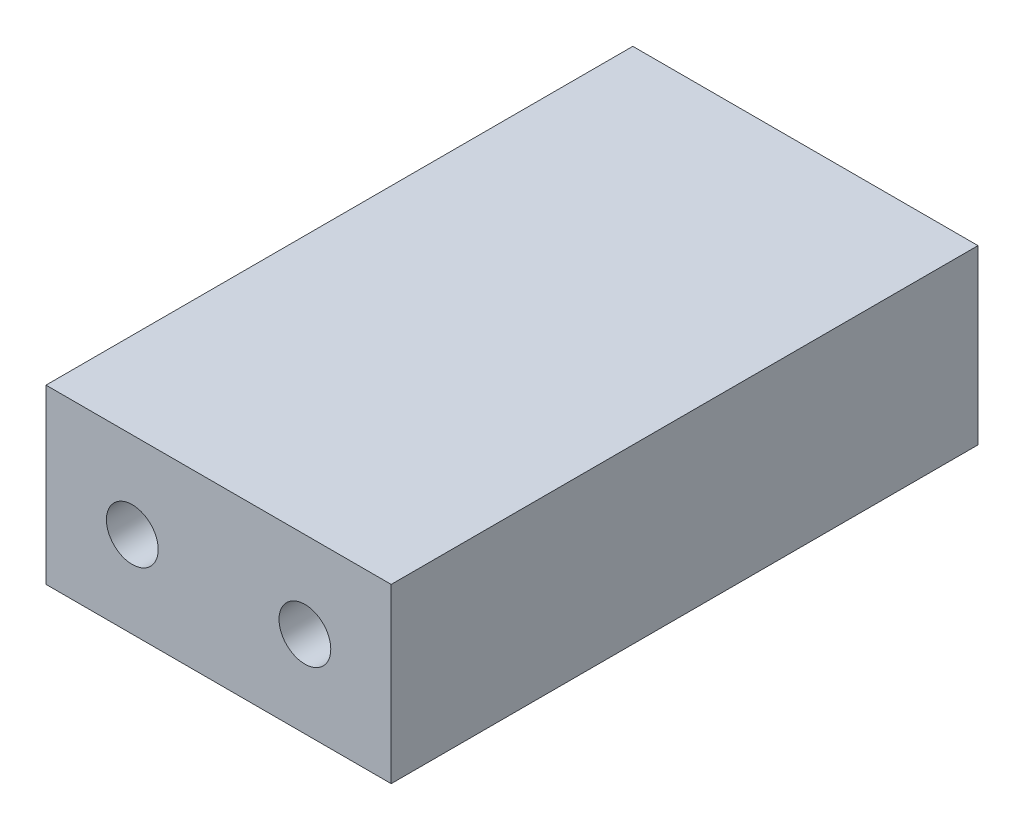
SolidWorks part; units mm, degrees
ref_plane "Front Plane" through (0, 0, 0) normal (0, 0, 1) x (1, 0, 0)
ref_plane "Top Plane" through (0, 0, 0) normal (0, 1, 0) x (1, 0, 0)
ref_plane "Right Plane" through (0, 0, 0) normal (1, 0, 0) x (0, 0, -1)
sketch "Sketch2" plane through (0, 0, 0) normal (0, 0, 1) x (1, 0, 0)
  line L1 (-10, -5) -> (10, -5)
  line L2 (-10, -5) -> (-10, 5)
  line L3 (-10, 5) -> (10, 5)
  line L4 (10, -5) -> (10, 5)
  line L5 (-10, -5) -> (10, 5) construction
  line L6 (-10, 5) -> (10, -5) construction
  point P0 (0, 0)
  dimension "D1" = 10
  dimension "D2" = 20
extrude "Boss-Extrude1" add sketch "Sketch2" along normal blind 34
sketch "Sketch3" plane through (0, 0, 34) normal (0, 0, 1) x (1, 0, 0)
  line L0 (0, 0) -> (-5, 0)
  line L1 (0, 0) -> (5, 0)
  circle A0 centre (-5, 0) radius 1.5
  circle A1 centre (5, 0) radius 1.5
  dimension "D2" = 3
  dimension "D4" = 3
  dimension "D1" = 5
  dimension "D3" = 5
extrude "Cut-Extrude1" cut sketch "Sketch3" against normal blind 6 contours A0 | A1 region at (-6.4576, 0, 34) region at (5, 1.4576, 34)
sketch "Sketch4" plane through (0, 0, 0) normal (0, 0, -1) x (-1, 0, 0)
  line L0 (0, 0) -> (-5, 0)
  line L1 (0, 0) -> (5, 0)
  circle A0 centre (-5, 0) radius 1.5
  circle A1 centre (5, 0) radius 1.5
  dimension "D2" = 3
  dimension "D4" = 3
  dimension "D1" = 5
  dimension "D3" = 5
extrude "Cut-Extrude2" cut sketch "Sketch4" against normal blind 6 contours A0 | A1 region at (6.4576, 0, 0) region at (-5, 1.4576, 0)
